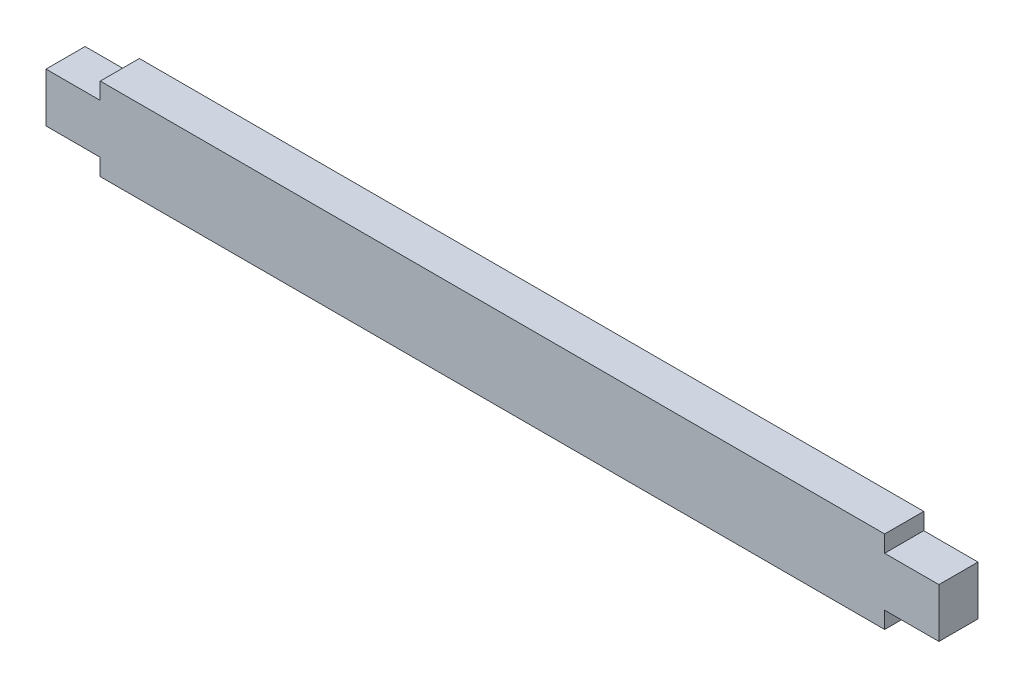
SolidWorks part; units mm, degrees
ref_plane "Front Plane" through (0, 0, 0) normal (0, 0, 1) x (1, 0, 0)
ref_plane "Top Plane" through (0, 0, 0) normal (0, 1, 0) x (1, 0, 0)
ref_plane "Right Plane" through (0, 0, 0) normal (1, 0, 0) x (0, 0, -1)
ref_plane "Plane1" through (0, 0, 56.5394) normal (0, 0, 1) x (1, 0, 0)
ref_plane "Plane2" through (0, 0, 37.4894) normal (0, 0, 1) x (1, 0, 0)
ref_axis "Axis1" through (-60.1851, 206.9434, 37.4894) along (0, -1, 0)
ref_axis "Axis2" through (60.1851, 44.8, 37.4894) along (0, 1, 0)
ref_plane "Plane3" through (0, 0, 43.4894) normal (0, 0, 1) x (1, 0, 0)
ref_axis "Axis3" through (-68.5096, 181.61, 43.4894) along (0, 1, 0)
ref_axis "Axis4" through (68.5096, 202.61, 43.4894) along (0, -1, 0)
sketch "Sketch2" plane through (0, 0, 37.4894) normal (0, 0, 1) x (1, 0, 0)
  line L0 (-60.1851, 183.6025) -> (-60.1851, 50183.6025) construction
  line L1 (-60.1851, 206.9434) -> (-60.1851, 181.61) construction
  line L2 (60.1851, 168.474) -> (60.1851, 50168.474) construction
  line L3 (60.1851, 44.8) -> (60.1851, 259.1528) construction
  line L4 (-60.1851, 232.3068) -> (60.1851, 232.3068)
  line L5 (60.1851, 232.3068) -> (60.1851, 229.7369)
  line L6 (60.1851, 229.7369) -> (68.5096, 229.7369)
  line L9 (-60.1851, 219.6068) -> (-60.1851, 222.1767)
  line L10 (-60.1851, 222.1767) -> (-68.5096, 222.1767)
  line L11 (-68.5096, 222.1767) -> (-68.5096, 229.7369)
  line L12 (-68.5096, 229.7369) -> (-60.1851, 229.7369)
  line L13 (-60.1851, 229.7369) -> (-60.1851, 232.3068)
  line L14 (-60.1851, 219.6068) -> (60.1851, 219.6068)
  line L15 (60.1851, 219.6068) -> (60.1851, 222.1767)
  line L16 (60.1851, 222.1767) -> (68.5096, 222.1767)
  line L17 (68.5096, 222.1767) -> (68.5096, 229.7369)
  line L18 (-68.5096, 181.61) -> (-68.5096, 202.61) construction
  line L20 (-64.7351, 235.3859) -> (-70.4272, 235.3859) construction
  dimension "D1" = 12.7
  dimension "D2" = 7.5602
  dimension "D3" = 3.0791
extrude "Boss-Extrude1" add sketch "Sketch2" along normal blind 6
